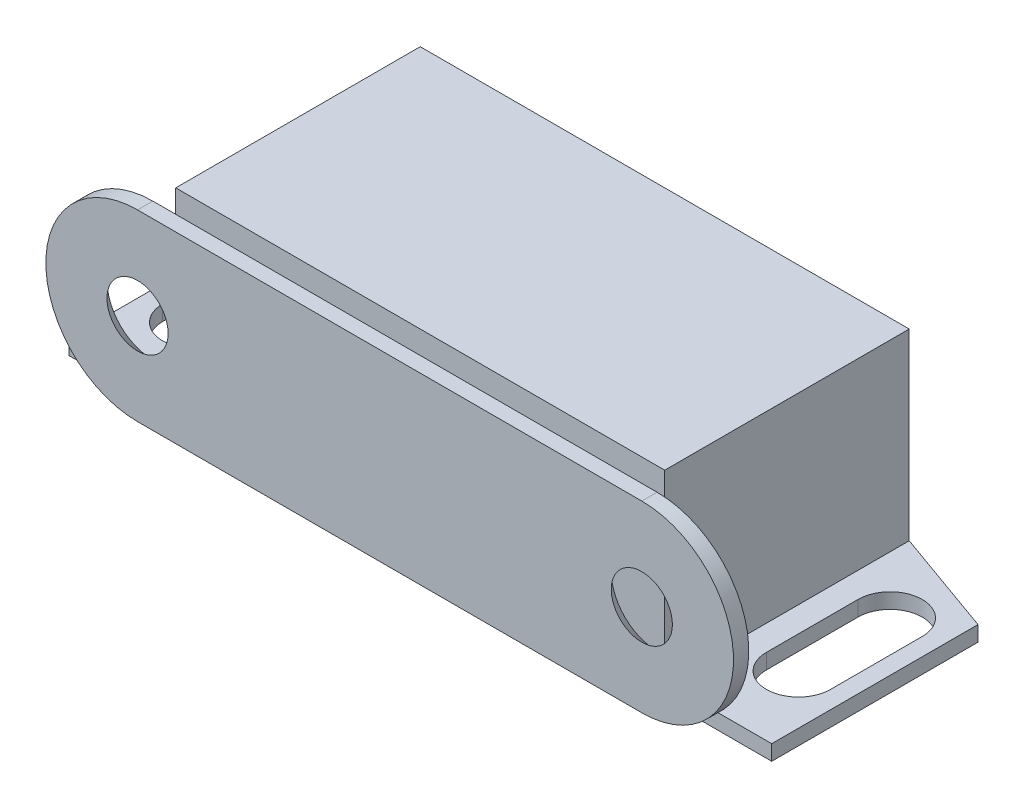
SolidWorks part; units mm, degrees
ref_plane "前视基准面" through (0, 0, 0) normal (0, 0, 1) x (1, 0, 0)
ref_plane "上视基准面" through (0, 0, 0) normal (0, 1, 0) x (1, 0, 0)
ref_plane "右视基准面" through (0, 0, 0) normal (1, 0, 0) x (0, 0, -1)
sketch "草图1" plane through (0, 0, 0) normal (0, 0, 1) x (1, 0, 0)
  line L0 (0, 0) -> (8, 0)
  line L1 (8, 0) -> (8, 12)
  line L2 (8, 12) -> (38, 12)
  line L3 (38, 12) -> (38, 0)
  line L4 (38, 0) -> (46, 0)
  line L5 (0, 0) -> (0, 1)
  line L6 (0, 1) -> (7, 1)
  line L7 (7, 1) -> (7, 13)
  line L8 (7, 13) -> (39, 13)
  line L9 (39, 13) -> (39, 1)
  line L10 (39, 1) -> (46, 1)
  line L11 (46, 1) -> (46, 0)
  line L12 (8, 0) -> (38, 0)
  line L13 (23, 13) -> (23, -4.1188) construction
  dimension "D1" = 1
  dimension "D2" = 13
  dimension "D3" = 1
  dimension "D4" = 1
  dimension "D5" = 1
  dimension "D6" = 1
  dimension "D7" = 32
  dimension "D8" = 46
extrude "凸台-拉伸1" add sketch "草图1" against normal blind 16 contours L13 L2 L1 L12 | L2 L13 L12 L3 | L13 L8 L7 L6 L5 L0 L1 L2 | L8 L13 L2 L3 L4 L11 L10 L9 region at (0.2642, 0.5, 0) region at (15.5, 6, 0) region at (30.5, 6, 0) region at (23.2642, 12.5, 0)
sketch "草图2" plane through (0, 1, 0) normal (0, 1, 0) x (1, 0, 0)
  line L0 (42.75, 5) -> (42.75, 11) construction
  line L1 (40.65, 5) -> (40.65, 11)
  line L2 (44.85, 5) -> (44.85, 11)
  line L3 (23, 16) -> (23, 11.3545) construction
  line L4 (7, 16) -> (39, 16) construction
  line L5 (3.25, 5) -> (3.25, 11) construction
  line L6 (5.35, 5) -> (5.35, 11)
  line L7 (1.15, 5) -> (1.15, 11)
  line L8 (0, 8) -> (46, 8) construction
  line L9 (0, 16) -> (0, 0) construction
  line L10 (46, 16) -> (46, 0) construction
  arc A0 (40.65, 5) -> (44.85, 5) centre (42.75, 5) ccw
  arc A1 (44.85, 11) -> (40.65, 11) centre (42.75, 11) ccw
  arc A2 (5.35, 5) -> (1.15, 5) centre (3.25, 5) cw
  arc A3 (1.15, 11) -> (5.35, 11) centre (3.25, 11) cw
  point P2 (42.75, 8)
  point P13 (3.25, 8)
  point P24 (42.75, 8)
  point P25 (42.75, 8)
  point P26 (42.75, 5.7006)
  dimension "D1" = 39.5
  dimension "D2" = 4.2
  dimension "D3" = 6
extrude "切除-拉伸1" cut sketch "草图2" against normal blind 16
sketch "草图3" plane through (0, 1, 0) normal (0, 1, 0) x (1, 0, 0)
  line L0 (39, 16) -> (46, 13.5)
  line L1 (46, 16) -> (46, 0) construction
  line L2 (46, 13.5) -> (46, 16)
  line L3 (46, 16) -> (39, 16)
  line L4 (23, 16) -> (23, 13.5) construction
  line L5 (7, 16) -> (39, 16) construction
  line L6 (0, 16) -> (7, 16)
  line L7 (0, 13.5) -> (0, 16)
  line L8 (7, 16) -> (0, 13.5)
  dimension "D1" = 2.5
extrude "切除-拉伸2" cut sketch "草图3" against normal blind 16
sketch "草图4" plane through (0, 0, 0) normal (0, 0, 1) x (1, 0, 0)
  line L0 (23, 13) -> (23, 0) construction
  line L1 (7, 13) -> (39, 13) construction
  line L2 (0, 0) -> (46, 0) construction
  line L4 (12, 9) -> (34, 9)
  line L5 (12, 9) -> (12, 10)
  line L6 (12, 10) -> (34, 10)
  line L7 (34, 9) -> (34, 10)
  line L8 (12, 9) -> (34, 10) construction
  line L9 (12, 10) -> (34, 9) construction
  line L10 (12, 4) -> (34, 4)
  line L11 (12, 4) -> (12, 5)
  line L12 (12, 5) -> (34, 5)
  line L13 (34, 4) -> (34, 5)
  line L14 (12, 4) -> (34, 5) construction
  line L15 (12, 5) -> (34, 4) construction
  point P6 (23, 9.5)
  point P11 (23, 4.5)
  dimension "D1" = 1
  dimension "D2" = 1
  dimension "D3" = 3
  dimension "D4" = 4
  dimension "D5" = 22
  dimension "D6" = 22
extrude "凸台-拉伸2" add sketch "草图4" along normal blind 1
sketch "草图5" plane through (0, 0, 1) normal (0, 0, 1) x (1, 0, 0)
  line L0 (23, 13) -> (23, 0) construction
  line L1 (7, 13) -> (39, 13) construction
  line L2 (0, 0) -> (46, 0) construction
  line L3 (6.5, 6.5) -> (39.5, 6.5) construction
  line L4 (6.5, 12.5) -> (39.5, 12.5)
  line L5 (6.5, 0.5) -> (39.5, 0.5)
  arc A0 (6.5, 12.5) -> (6.5, 0.5) centre (6.5, 6.5) ccw
  arc A1 (39.5, 0.5) -> (39.5, 12.5) centre (39.5, 6.5) ccw
  circle A2 centre (6.5, 6.5) radius 2
  circle A3 centre (39.5, 6.5) radius 2
  point P8 (23, 6.5)
  point P13 (0.5, 6.5)
  point P14 (45.5, 6.5)
  dimension "D3" = 4
  dimension "D1" = 45
  dimension "D2" = 12
  dimension "D4" = 33
extrude "凸台-拉伸3" add sketch "草图5" along normal blind 1 separate body
chamfer "倒角1" distance 1 angle 45 2 edges at (8.5, 6.5, 1) (41.5, 6.5, 1)
